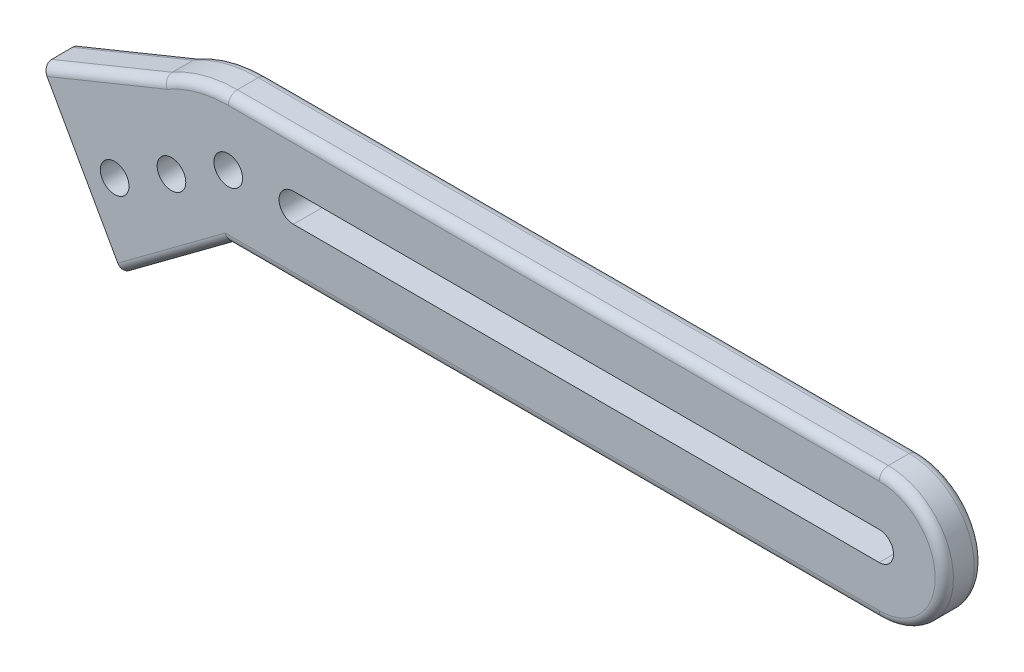
SolidWorks part; units mm, degrees
ref_plane "前视基准面" through (0, 0, 0) normal (0, 0, 1) x (1, 0, 0)
ref_plane "上视基准面" through (0, 0, 0) normal (0, 1, 0) x (1, 0, 0)
ref_plane "右视基准面" through (0, 0, 0) normal (1, 0, 0) x (0, 0, -1)
other "Configuration Table"
sketch "草图1" plane through (0, 0, 0) normal (0, 0, 1) x (1, 0, 0)
  line L0 (0, -55) -> (0, 55) construction
  line L1 (0, 5) -> (50, 5)
  line L3 (0, -5) -> (50, -5)
  line L5 (55, 0) -> (-55, 0) construction
  line L13 (0, -5) -> (-176.616, -136.1747)
  line L14 (-5, 3.6603) -> (-208.7523, -79.3156)
  arc A0 (50, -5) -> (50, 5) centre (50, 0) ccw
  arc A3 (0, 5) -> (-5, 3.6603) centre (0, -5) ccw
  arc A7 (-208.7523, -79.3156) -> (-176.616, -136.1747) centre (-192.6841, -107.7451) ccw
  dimension "D4" = 5
  dimension "D9" = 220
  dimension "D7" = 5
  dimension "D10" = 5
  dimension "D5" = 220
  dimension "D11" = 32.6562
  dimension "D1" = 50
  dimension "D2" = 10
  dimension "D3" = 5
  dimension "D6" = 202.158
  dimension "D8" = 143.398
extrude "凸台-拉伸1" add sketch "草图1" along normal blind 3
sketch "草图3" plane through (0, 0, 3) normal (0, 0, 1) x (1, 0, 0)
  line L1 (5, 1.1) -> (50, 1.1)
  line L3 (5, -1.1) -> (50, -1.1)
  line L5 (55, 0) -> (-55, 0) construction
  line L6 (0, -55) -> (0, 55) construction
  arc A0 (50, -1.1) -> (50, 1.1) centre (50, 0) ccw
  arc A1 (5, 1.1) -> (5, -1.1) centre (5, 0) ccw
  dimension "D5" = 45
  dimension "D1" = 1.1
  dimension "D4" = 1.1
  dimension "D2" = 2.2
  dimension "D3" = 1.1
  dimension "D6" = 5
  dimension "D7" = 5
extrude "切除-拉伸1" cut sketch "草图3" against normal blind 3
sketch "草图4" plane through (0, 0, 3) normal (0, 0, 1) x (1, 0, 0)
  line L0 (0, 0) -> (-221.1137, -123.8133)
  arc A1 (-208.7523, -79.3156) -> (-176.616, -136.1747) centre (-192.6841, -107.7451) ccw construction
ref_plane "基准面1" through (0, 0, 0) normal (-0.4886, 0.8725, 0) x (-0.8725, -0.4886, 0)
hole_wizard "Ø2.2 (2.2) 直径孔1" positions "草图7" profile "草图8" hole size "Ø2.2" standard "ANSI Metric" end condition up to next
sketch "草图7" plane through (0, 0, 3) normal (0, 0, 1) x (1, 0, 0)
  line L0 (0, 0) -> (-221.1137, -123.8133) construction
  line L1 (0, -1.65) -> (0, 1.65) construction
  point P1 (0, 0)
  dimension "D1" = 0
sketch "草图8" plane through (0, 0, 3) normal (1, 0, 0) x (0, -1, 0)
  line L0 (0, 0) -> (0, 3)
  line L1 (0, 3) -> (1.1, 3)
  line L2 (1.1, 3) -> (1.1, 0)
  line L5 (1.1, 0) -> (0, 0)
  line L11 (0, -6.35) -> (0, 107.95) construction
  dimension "通孔孔直径" = 2.2
  dimension "通孔孔深度" = 3
pattern_linear "阵列(线性)1" count 10 spacing 5 along (-0.8725, -0.4886, 0) of "Ø2.2 (2.2) 直径孔1"
fillet "圆角1" radius 0.7 14 edges at (55, 0, 0) (55, 0, 3) (25, 5, 3) (-2.5882, 4.6593, 3) (-2.5882, 4.6593, 0) (25, 5, 0) (25, -5, 0) (25, -5, 3) (-106.8762, -37.8277, 3) (-106.8762, -37.8277, 0) (-88.308, -70.5873, 0) (-88.308, -70.5873, 3) (-221.1137, -123.8133, 0) (-221.1137, -123.8133, 3)
sketch "草图9" plane through (0, 0, 3) normal (0, 0, 1) x (1, 0, 0)
  line L0 (125.6956, 70.3837) -> (-125.6956, -70.3837) construction
  line L1 (-7.2455, -12.6453) -> (-190.5427, -170.2592)
  line L2 (-190.5427, -170.2592) -> (-265.1746, -79.6562)
  line L3 (-265.1746, -79.6562) -> (-19.2123, 8.7257)
  line L5 (-10.9065, -6.1072) -> (-7.2455, -12.6453)
  line L6 (-10.9065, -6.1072) -> (-19.2123, 8.7257)
  dimension "D1" = 17
  dimension "D2" = 90
  dimension "D3" = 60.0551
  dimension "D4" = 55.4613
  dimension "D5" = 236.9369
  dimension "D6" = 261.3596
  dimension "D7" = 7.4934
  dimension "D8" = 90
  dimension "D9" = 12.5
  dimension "D10" = 10.9065
extrude "切除-拉伸2" cut sketch "草图9" against normal through all
